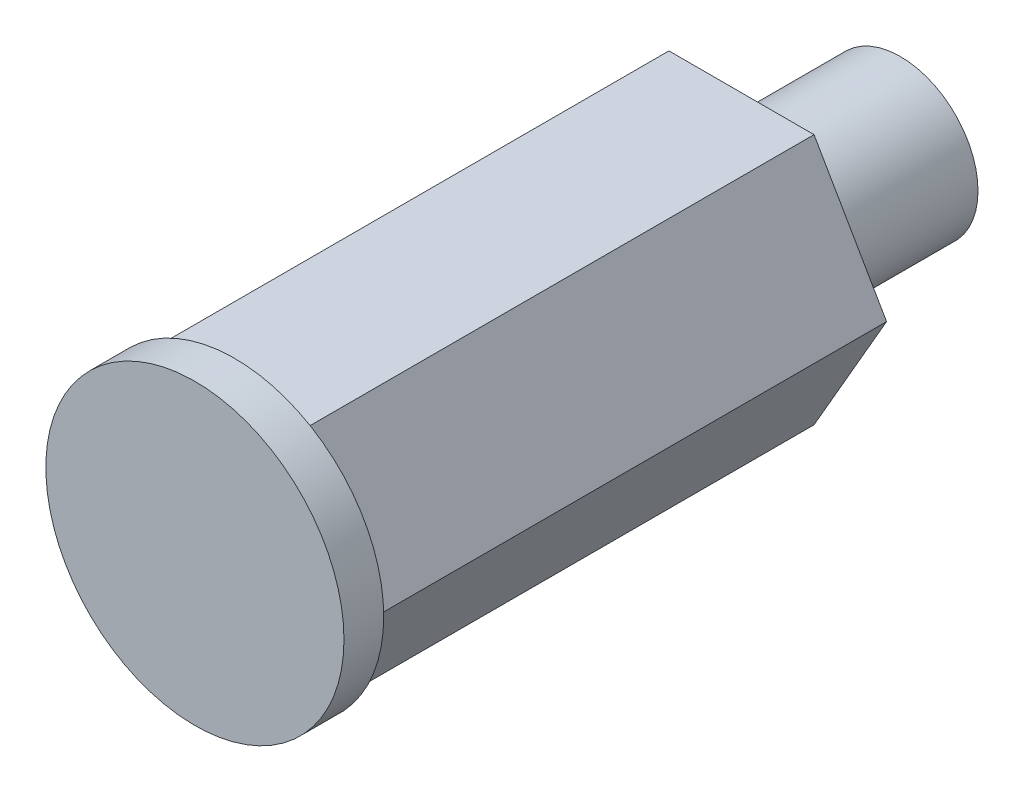
SolidWorks part; units mm, degrees
ref_plane "Front Plane" through (0, 0, 0) normal (0, 0, 1) x (1, 0, 0)
ref_plane "Top Plane" through (0, 0, 0) normal (0, 1, 0) x (1, 0, 0)
ref_plane "Right Plane" through (0, 0, 0) normal (1, 0, 0) x (0, 0, -1)
sketch "Sketch1" plane through (0, 0, 0) normal (0, 0, 1) x (1, 0, 0)
  line L0 (-1.9442, -2.015) -> (-1.9442, 2.015)
  line L1 (-1.9442, -2.015) -> (1.9442, -2.015) construction
  line L2 (-1.9442, -2.015) -> (-1.9442, 2.015) construction
  line L3 (-1.9442, 2.015) -> (1.9442, 2.015) construction
  line L4 (1.9442, -2.015) -> (1.9442, 2.015) construction
  line L5 (-1.9442, -2.015) -> (1.9442, 2.015) construction
  line L6 (-1.9442, 2.015) -> (1.9442, -2.015) construction
  line L7 (1.9442, -2.015) -> (1.9442, 2.015)
  circle A0 centre (0, 0) radius 2.8 construction
  arc A1 (-1.9442, 2.015) -> (1.9442, 2.015) centre (0, 0) cw
  arc A2 (-1.9442, -2.015) -> (1.9442, -2.015) centre (0, 0) ccw
  circle A3 centre (0, 0) radius 3.9
  dimension "D1" = 5.6
  dimension "D3" = 7.8
  dimension "D2" = 4.03
extrude "Boss-Extrude1" add sketch "Sketch1" along normal blind 8
sketch "Sketch2" plane through (0, 0, 8) normal (0, 0, 1) x (1, 0, 0)
  line L7 (3.65, 6.322) -> (-3.65, 6.322)
  line L8 (-3.65, 6.322) -> (-7.3, 0)
  line L9 (-7.3, 0) -> (-3.65, -6.322)
  line L10 (-3.65, -6.322) -> (3.65, -6.322)
  line L11 (3.65, -6.322) -> (7.3, 0)
  line L12 (7.3, 0) -> (3.65, 6.322)
  circle A0 centre (0, 0) radius 6.322 construction
  point P1 (0, 6.322)
  dimension "D1" = 7.3
extrude "Boss-Extrude2" add sketch "Sketch2" along normal blind 25.5 contours L7 L8 L9 L10 L11 L12
sketch "Sketch3" plane through (0, 0, 33.5) normal (0, 0, 1) x (1, 0, 0)
  circle A0 centre (0, 0) radius 7.5
  dimension "D1" = 15
extrude "Boss-Extrude3" add sketch "Sketch3" along normal blind 2
